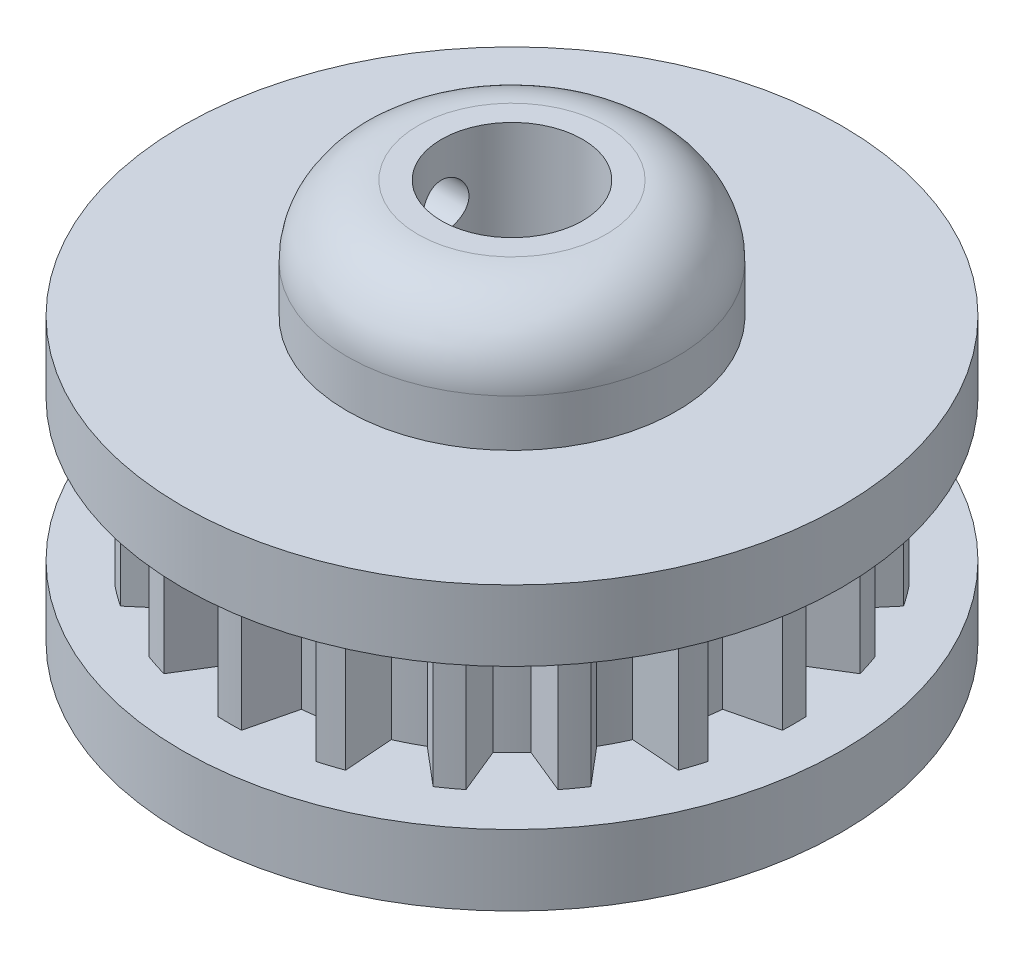
SolidWorks part; units mm, degrees
ref_plane "Front Plane" through (0, 0, 0) normal (0, 0, 1) x (1, 0, 0)
ref_plane "Top Plane" through (0, 0, 0) normal (0, 1, 0) x (1, 0, 0)
ref_plane "Right Plane" through (0, 0, 0) normal (1, 0, 0) x (0, 0, -1)
sketch "Sketch3" plane through (0, 0, 0) normal (0, 1, 0) x (1, 0, 0)
  line L0 (0, 12) -> (0, 10) construction
  line L1 (1, 9.9499) -> (0.5, 11.9896)
  line L2 (-1, 9.9499) -> (-0.5, 11.9896)
  line L3 (4.0257, 9.1539) -> (4.1805, 11.2483)
  line L4 (2.1236, 9.7719) -> (3.2295, 11.5573)
  line L5 (6.6574, 7.4618) -> (7.4518, 9.4059)
  line L6 (5.0394, 8.6374) -> (6.6428, 9.9937)
  line L7 (8.6374, 5.0394) -> (9.9937, 6.6428)
  line L8 (7.4618, 6.6574) -> (9.4059, 7.4518)
  line L9 (9.7719, 2.1236) -> (11.5573, 3.2295)
  line L10 (9.1539, 4.0257) -> (11.2483, 4.1805)
  line L11 (9.9499, -1) -> (11.9896, -0.5)
  line L12 (9.9499, 1) -> (11.9896, 0.5)
  line L13 (9.1539, -4.0257) -> (11.2483, -4.1805)
  line L14 (9.7719, -2.1236) -> (11.5573, -3.2295)
  line L15 (7.4618, -6.6574) -> (9.4059, -7.4518)
  line L16 (8.6374, -5.0394) -> (9.9937, -6.6428)
  line L17 (5.0394, -8.6374) -> (6.6428, -9.9937)
  line L18 (6.6574, -7.4618) -> (7.4518, -9.4059)
  line L19 (2.1236, -9.7719) -> (3.2295, -11.5573)
  line L20 (4.0257, -9.1539) -> (4.1805, -11.2483)
  line L21 (-1, -9.9499) -> (-0.5, -11.9896)
  line L22 (1, -9.9499) -> (0.5, -11.9896)
  line L23 (-4.0257, -9.1539) -> (-4.1805, -11.2483)
  line L24 (-2.1236, -9.7719) -> (-3.2295, -11.5573)
  line L25 (-6.6574, -7.4618) -> (-7.4518, -9.4059)
  line L26 (-5.0394, -8.6374) -> (-6.6428, -9.9937)
  line L27 (-8.6374, -5.0394) -> (-9.9937, -6.6428)
  line L28 (-7.4618, -6.6574) -> (-9.4059, -7.4518)
  line L29 (-9.7719, -2.1236) -> (-11.5573, -3.2295)
  line L30 (-9.1539, -4.0257) -> (-11.2483, -4.1805)
  line L31 (-9.9499, 1) -> (-11.9896, 0.5)
  line L32 (-9.9499, -1) -> (-11.9896, -0.5)
  line L33 (-9.1539, 4.0257) -> (-11.2483, 4.1805)
  line L34 (-9.7719, 2.1236) -> (-11.5573, 3.2295)
  line L35 (-7.4618, 6.6574) -> (-9.4059, 7.4518)
  line L36 (-8.6374, 5.0394) -> (-9.9937, 6.6428)
  line L37 (-5.0394, 8.6374) -> (-6.6428, 9.9937)
  line L38 (-6.6574, 7.4618) -> (-7.4518, 9.4059)
  line L39 (-2.1236, 9.7719) -> (-3.2295, 11.5573)
  line L40 (-4.0257, 9.1539) -> (-4.1805, 11.2483)
  circle A0 centre (0, 0) radius 3
  circle A1 centre (0, 0) radius 12 construction
  arc A2 (-1, 9.9499) -> (-2.1236, 9.7719) centre (0, 0) ccw
  arc A3 (0.5, 11.9896) -> (-0.5, 11.9896) centre (0, 0) ccw
  arc A4 (4.1805, 11.2483) -> (3.2295, 11.5573) centre (0, 0) ccw
  arc A5 (7.4518, 9.4059) -> (6.6428, 9.9937) centre (0, 0) ccw
  arc A6 (9.9937, 6.6428) -> (9.4059, 7.4518) centre (0, 0) ccw
  arc A7 (11.5573, 3.2295) -> (11.2483, 4.1805) centre (0, 0) ccw
  arc A8 (11.9896, -0.5) -> (11.9896, 0.5) centre (0, 0) ccw
  arc A9 (11.2483, -4.1805) -> (11.5573, -3.2295) centre (0, 0) ccw
  arc A10 (9.4059, -7.4518) -> (9.9937, -6.6428) centre (0, 0) ccw
  arc A11 (6.6428, -9.9937) -> (7.4518, -9.4059) centre (0, 0) ccw
  arc A12 (3.2295, -11.5573) -> (4.1805, -11.2483) centre (0, 0) ccw
  arc A13 (-0.5, -11.9896) -> (0.5, -11.9896) centre (0, 0) ccw
  arc A14 (-4.1805, -11.2483) -> (-3.2295, -11.5573) centre (0, 0) ccw
  arc A15 (-7.4518, -9.4059) -> (-6.6428, -9.9937) centre (0, 0) ccw
  arc A16 (-9.9937, -6.6428) -> (-9.4059, -7.4518) centre (0, 0) ccw
  arc A17 (-11.5573, -3.2295) -> (-11.2483, -4.1805) centre (0, 0) ccw
  arc A18 (-11.9896, 0.5) -> (-11.9896, -0.5) centre (0, 0) ccw
  arc A19 (-11.2483, 4.1805) -> (-11.5573, 3.2295) centre (0, 0) ccw
  arc A20 (-9.4059, 7.4518) -> (-9.9937, 6.6428) centre (0, 0) ccw
  arc A21 (-6.6428, 9.9937) -> (-7.4518, 9.4059) centre (0, 0) ccw
  arc A22 (-3.2295, 11.5573) -> (-4.1805, 11.2483) centre (0, 0) ccw
  arc A23 (-4.0257, 9.1539) -> (-5.0394, 8.6374) centre (0, 0) ccw
  arc A24 (-6.6574, 7.4618) -> (-7.4618, 6.6574) centre (0, 0) ccw
  arc A25 (-8.6374, 5.0394) -> (-9.1539, 4.0257) centre (0, 0) ccw
  arc A26 (-9.7719, 2.1236) -> (-9.9499, 1) centre (0, 0) ccw
  arc A27 (-9.9499, -1) -> (-9.7719, -2.1236) centre (0, 0) ccw
  arc A28 (-9.1539, -4.0257) -> (-8.6374, -5.0394) centre (0, 0) ccw
  arc A29 (2.1236, 9.7719) -> (1, 9.9499) centre (0, 0) ccw
  arc A30 (5.0394, 8.6374) -> (4.0257, 9.1539) centre (0, 0) ccw
  arc A31 (7.4618, 6.6574) -> (6.6574, 7.4618) centre (0, 0) ccw
  arc A32 (9.1539, 4.0257) -> (8.6374, 5.0394) centre (0, 0) ccw
  arc A33 (9.9499, 1) -> (9.7719, 2.1236) centre (0, 0) ccw
  arc A34 (9.7719, -2.1236) -> (9.9499, -1) centre (0, 0) ccw
  arc A35 (8.6374, -5.0394) -> (9.1539, -4.0257) centre (0, 0) ccw
  arc A36 (6.6574, -7.4618) -> (7.4618, -6.6574) centre (0, 0) ccw
  arc A37 (4.0257, -9.1539) -> (5.0394, -8.6374) centre (0, 0) ccw
  arc A38 (1, -9.9499) -> (2.1236, -9.7719) centre (0, 0) ccw
  arc A39 (-2.1236, -9.7719) -> (-1, -9.9499) centre (0, 0) ccw
  arc A40 (-5.0394, -8.6374) -> (-4.0257, -9.1539) centre (0, 0) ccw
  arc A41 (-7.4618, -6.6574) -> (-6.6574, -7.4618) centre (0, 0) ccw
  point P90 (0, 0)
  dimension "D1" = 24
  dimension "D2" = 6
  dimension "D3" = 20
  dimension "D4" = 1
  dimension "D5" = 0.5
  dimension "D6" = 20
extrude "Boss-Extrude2" add sketch "Sketch3" along normal blind 6
sketch "Sketch4" plane through (0, 0, 0) normal (1, 0, 0) x (0, 0, -1)
  line L0 (0, -1000) -> (0, 49000) construction
  line L1 (0, 6) -> (14, 6)
  line L2 (0.5, 6) -> (-0.5, 6) construction
  line L3 (14, 6) -> (14, 9)
  line L4 (14, 9) -> (7, 9)
  line L5 (7, 9) -> (7, 14)
  line L6 (7, 14) -> (0, 14)
  line L7 (0, 14) -> (0, 6)
  line L8 (-1011.9896, 3) -> (48988.0104, 3) construction
  line L9 (-11.9896, 6) -> (-11.9896, 0) construction
  line L10 (7, -8) -> (0, -8)
  line L11 (7, -3) -> (7, -8)
  line L12 (14, -3) -> (7, -3)
  line L13 (14, 0) -> (14, -3)
  line L14 (0, 0) -> (14, 0)
  line L15 (0, -8) -> (0, 0)
  point P16 (-11.9896, 3)
  dimension "D1" = 14
  dimension "D2" = 7
  dimension "D3" = 8
  dimension "3" = 3
revolve "Revolve1" add sketch "Sketch4" angle 360 about L0 region at (0, -3.3182, -5.4091)
sketch "Sketch5" plane through (0, -8, 0) normal (0, -1, 0) x (1, 0, 0)
  circle A0 centre (0, 0) radius 3
  dimension "D1" = 6
extrude "Cut-Extrude1" cut sketch "Sketch5" against normal blind 27
sketch "Sketch6" plane through (0, 0, 0) normal (1, 0, 0) x (0, 0, -1)
  line L0 (0, 14) -> (0, 9) construction
  line L1 (7, 14) -> (-7, 14) construction
  line L2 (14, 9) -> (-14, 9) construction
  line L3 (-11.9896, 3) -> (11.9896, 3) construction
  line L4 (-11.9896, 6) -> (-11.9896, 0) construction
  line L5 (11.9896, 6) -> (11.9896, 0) construction
  circle A0 centre (0, 11.5) radius 1
  circle A1 centre (0, -5.5) radius 1
  dimension "D1" = 2
extrude "Cut-Extrude2" cut sketch "Sketch6" against normal blind 8
fillet "Fillet1" radius 3 2 edges at (0, -8, -7) (0, 14, -7)
